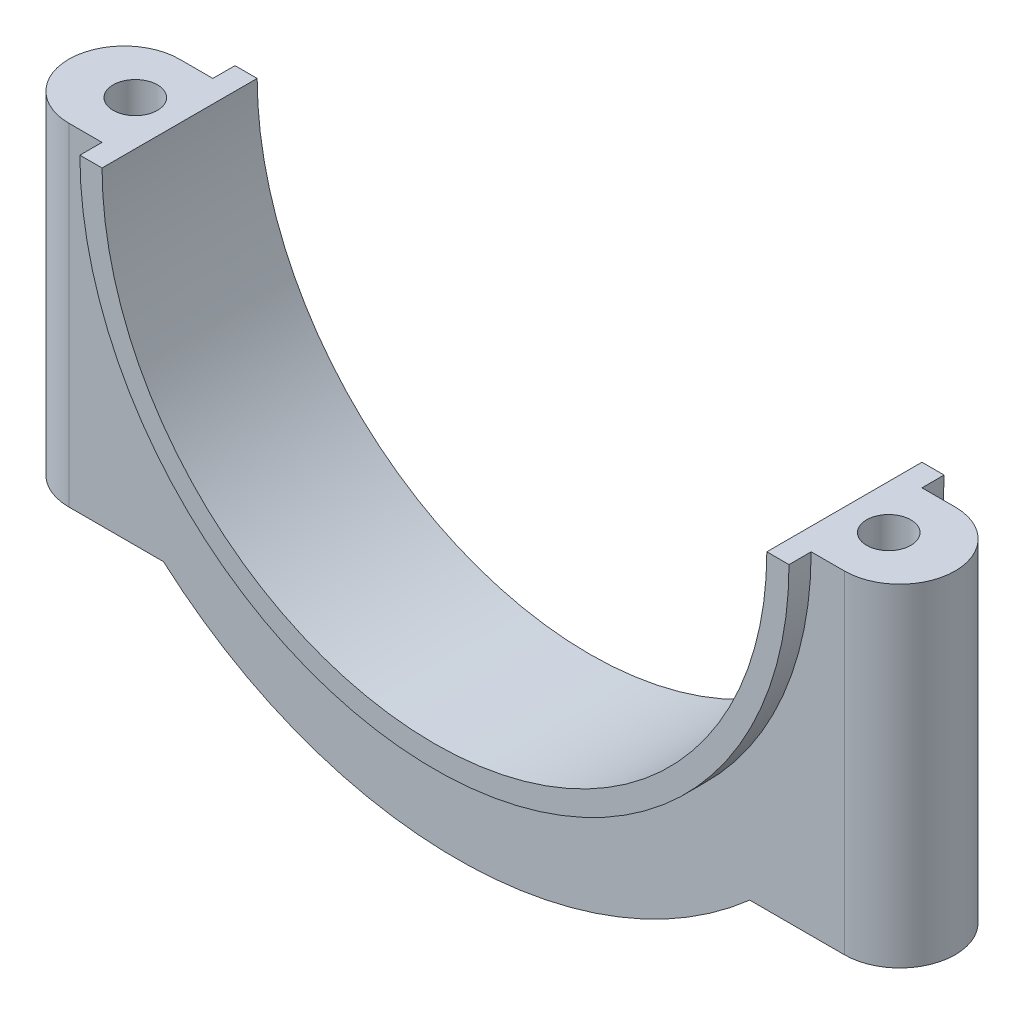
SolidWorks part; units mm, degrees
ref_plane "Front Plane" through (0, 0, 0) normal (0, 0, 1) x (1, 0, 0)
ref_plane "Top Plane" through (0, 0, 0) normal (0, 1, 0) x (1, 0, 0)
ref_plane "Right Plane" through (0, 0, 0) normal (1, 0, 0) x (0, 0, -1)
sketch "Sketch2" plane through (0, 0, 0) normal (0, 0, 1) x (1, 0, 0)
  line L1 (-20, 15) -> (-20, 0)
  line L2 (-20, 0) -> (-13.2288, 0)
  line L4 (20, 15) -> (20, 0)
  line L5 (20, 0) -> (13.2288, 0)
  line L7 (15, 15) -> (20, 15)
  line L8 (-20, 15) -> (-15, 15)
  arc A0 (-15, 15) -> (15, 15) centre (0, 15) ccw
  arc A1 (-13.2288, 0) -> (13.2288, 0) centre (0, 15) ccw
  point P1 (0, -5)
  point P3 (0, 0)
  point P9 (0, 0)
  dimension "D1" = 30
  dimension "D2" = 40
  dimension "D3" = 5
  dimension "D4" = 5
extrude "Boss-Extrude1" add sketch "Sketch2" along normal blind 5
sketch "Sketch3" plane through (0, 0, 5) normal (0, 0, 1) x (1, 0, 0)
  line L0 (-16, 15) -> (-15, 15)
  line L1 (15, 15) -> (16, 15)
  arc A2 (-15, 15) -> (15, 15) centre (0, 15) ccw
  arc A3 (-16, 15) -> (16, 15) centre (0, 15) ccw
  dimension "D1" = 32
extrude "Boss-Extrude2" add sketch "Sketch3" along normal blind 1
fillet "Fillet1" 2 edges at (20, 7.5, 5) (20, 7.5, 0) type full round first side face at (0, 4.875, 5) second side face at (0, 5, 0) middle face at (20, 7.5, 2.5)
fillet "Fillet2" 2 edges at (-20, 7.5, 0) (-20, 7.5, 5) type full round first side face at (-0.625, 5, 0) second side face at (-0.625, 4.875, 5) middle face at (-20, 7.5, 2.5)
extrude "Boss-Extrude3" add sketch "Sketch3<2>" against normal blind 6
sketch "Sketch3<2>" plane through (0, 0, 5) normal (0, 0, 1) x (1, 0, 0) same geometry as "Sketch3"
sketch "Sketch5" plane through (0, 15, 0) normal (0, 1, 0) x (1, 0, 0)
  line L0 (-16, -5) -> (-17.5, -5) construction
  line L1 (17.5, -5) -> (16, -5) construction
  circle A0 centre (-17, -2.5) radius 1
  circle A1 centre (17, -2.5) radius 1
  arc A2 (-17.5, 0) -> (-17.5, -5) centre (-17.5, -2.5) ccw construction
  arc A3 (17.5, -5) -> (17.5, 0) centre (17.5, -2.5) ccw construction
  point P9 (-20, -2.5)
  point P13 (20, -2.5)
  dimension "D2" = 2
  dimension "D4" = 2
  dimension "D5" = 3
  dimension "D1" = 2.5
  dimension "D3" = 3
  dimension "D6" = 2.5
extrude "Cut-Extrude2" cut sketch "Sketch5" against normal blind 15
